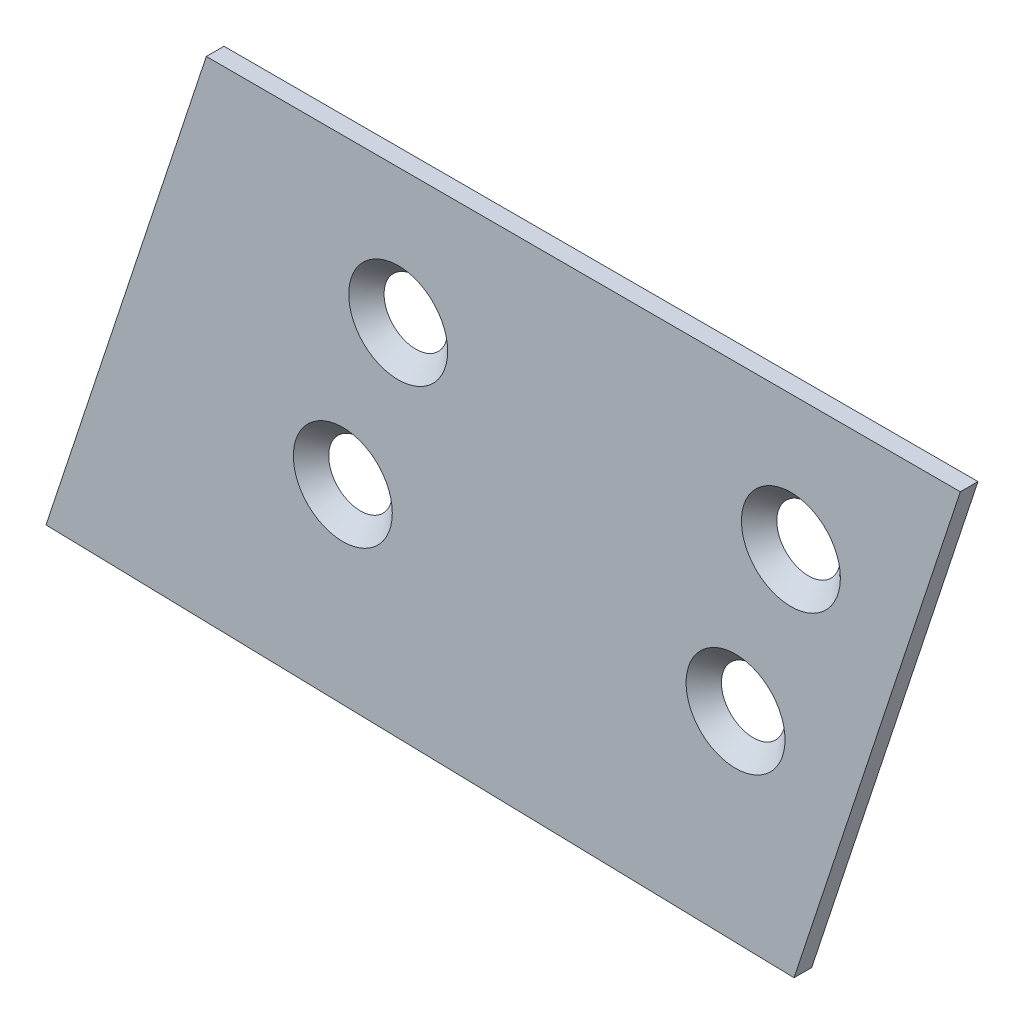
SolidWorks part; units mm, degrees
ref_plane "Front Plane" through (0, 0, 0) normal (0, 0, 1) x (1, 0, 0)
ref_plane "Top Plane" through (0, 0, 0) normal (0, 1, 0) x (1, 0, 0)
ref_plane "Right Plane" through (0, 0, 0) normal (1, 0, 0) x (0, 0, -1)
sketch "Sketch2" plane through (0, 0, 0) normal (0, 0, 1) x (1, 0, 0)
  line L0 (-54.6192, -24.5892) -> (30.7248, -24.5892)
  line L1 (-54.6192, -24.5892) -> (-71.4913, -75.7257)
  line L2 (30.7248, -24.5892) -> (13.8527, -75.7257)
  line L3 (-71.4913, -75.7257) -> (13.8527, -75.7257)
  dimension "D1" = 85.344
  dimension "D2" = 53.848
  dimension "D3" = 108.26
extrude "Boss-Extrude1" add sketch "Sketch2" along normal blind 2
sketch "Sketch3" plane through (0, 0, 2) normal (0, 0, 1) x (1, 0, 0)
  line L0 (-72.7647, -79.585) -> (11.9014, -81.6395)
  line L2 (-71.4913, -75.7257) -> (-72.7647, -79.585)
  line L3 (-72.7647, -79.585) -> (18.6346, -79.585) construction
  line L4 (-54.6192, -24.5892) -> (-71.4913, -75.7257) construction
  line L5 (13.8527, -75.7257) -> (11.9014, -81.6395)
  line L6 (13.8527, -75.7257) -> (30.7248, -24.5892) construction
  line L7 (-71.4913, -75.7257) -> (13.8527, -75.7257)
  dimension "D1" = 1.39
  dimension "D2" = 180
  dimension "D3" = 180
  dimension "D4" = 4.064
extrude "Boss-Extrude2" add sketch "Sketch3" against normal blind 2
sketch "Sketch4" plane through (0, 0, 2) normal (0, 0, 1) x (1, 0, 0)
  line L0 (-32.9007, -39.8292) -> (-39.1673, -58.8221) construction
  line L1 (-39.1673, -58.8221) -> (5.2827, -58.8221) construction
  line L2 (5.2827, -58.8221) -> (11.5493, -39.8292) construction
  line L3 (11.5493, -39.8292) -> (-32.9007, -39.8292) construction
  line L4 (-54.6192, -24.5892) -> (-72.7647, -79.585) construction
  line L5 (30.7248, -24.5892) -> (-54.6192, -24.5892) construction
  circle A0 centre (-32.9007, -39.8292) radius 2.5
  circle A1 centre (11.5493, -39.8292) radius 2.5
  circle A2 centre (5.2827, -58.8221) radius 2.5
  circle A3 centre (-39.1673, -58.8221) radius 2.5
  dimension "D1" = 5
  dimension "D2" = 44.45
  dimension "D3" = 20
  dimension "D4" = 25.4
  dimension "D5" = 15.24
extrude "Cut-Extrude2" cut sketch "Sketch4" against normal up to surface (2 mm away) up to face at (-21.1894, -52.6007, 0)
hole_wizard "CSK for M5 SFHCS1" positions "3DSketch1" profile "Sketch6" countersink size "M5" standard "ANSI Metric" end condition through all
sketch3d "3DSketch1"
  line L0 (-32.9007, -39.8292, 0) -> (-32.9007, -39.8292, 2) construction
  line L1 (11.5493, -39.8292, 0) -> (11.5493, -39.8292, 2) construction
  line L2 (5.2827, -58.8221, 0) -> (5.2827, -58.8221, 2) construction
  line L3 (-39.1673, -58.8221, 0) -> (-39.1673, -58.8221, 2) construction
  point P0 (-32.9007, -39.8292, 2)
  point P4 (11.5493, -39.8292, 2)
  point P8 (5.2827, -58.8221, 2)
  point P12 (-39.1673, -58.8221, 2)
sketch "Sketch6" plane through (-32.9007, -39.8292, 2) normal (1, 0, 0) x (0, -1, 0)
  line L0 (0, 0) -> (0, 2)
  line L1 (0, 2) -> (2.75, 2)
  line L2 (2.75, 2) -> (2.75, 2.85)
  line L3 (2.75, 2.85) -> (5.6, 0)
  line L5 (5.6, 0) -> (0, 0)
  line L6 (-2.75, 2.85) -> (-5.6, 0) construction
  line L11 (0, -6.35) -> (0, 107.95) construction
  dimension "Thru Hole Dia." = 5.5
  dimension "Thru Hole Depth" = 2
  dimension "Near C'Sink Dia." = 11.2
  dimension "Near C'Sink Angle" = 90
